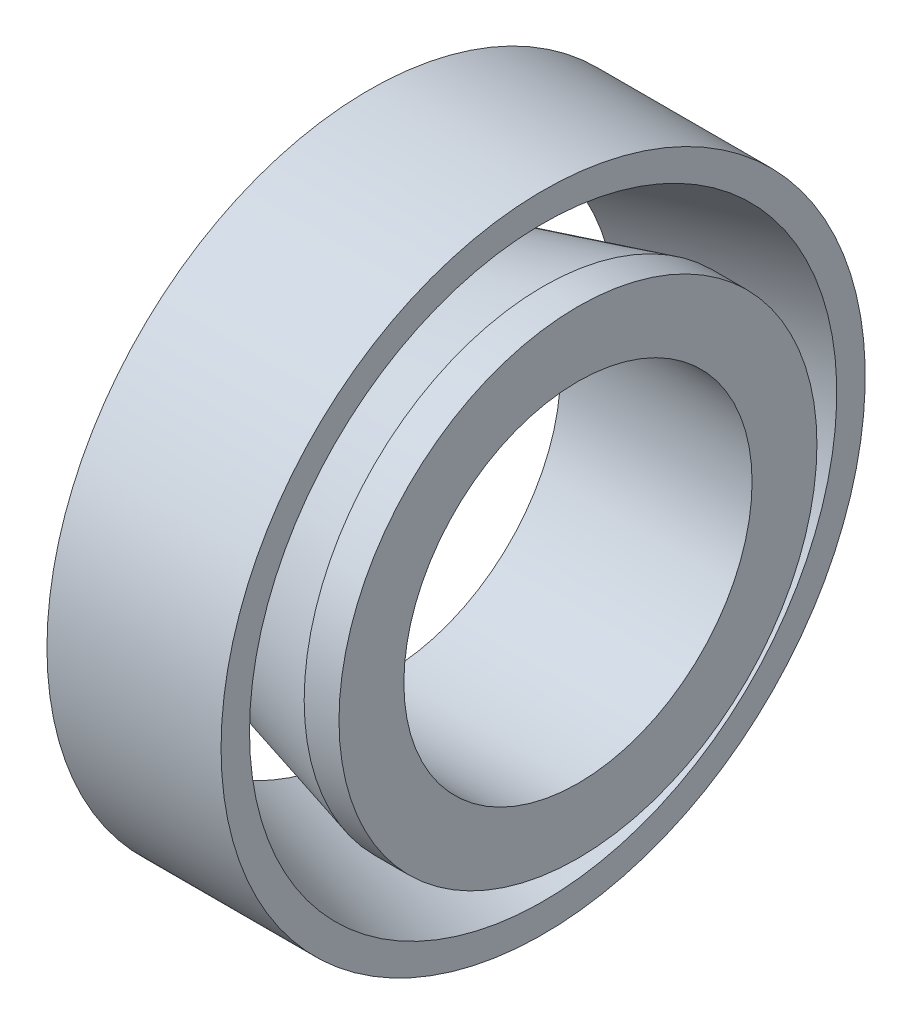
SolidWorks part; units mm, degrees
ref_plane "前视基准面" through (0, 0, 0) normal (0, 0, 1) x (1, 0, 0)
ref_plane "上视基准面" through (0, 0, 0) normal (0, 1, 0) x (1, 0, 0)
ref_plane "右视基准面" through (0, 0, 0) normal (1, 0, 0) x (0, 0, -1)
other "Configuration Table"
sketch "草图3" plane through (0, 0, 0) normal (0, 0, 1) x (1, 0, 0)
  line L0 (0, 0) -> (64.9069, 0) construction
  line L1 (0, 0) -> (0, 18.5) construction
  line L2 (0, 18.5) -> (10, 18.5)
  line L3 (10, 18.5) -> (10, 16.8656)
  line L4 (0, 18.5) -> (0, 14.1862)
  line L5 (0, 14.1862) -> (10, 16.8656)
  line L6 (1, 10) -> (12, 10)
  line L7 (12, 10) -> (12, 13.7257)
  line L8 (12, 13.7257) -> (10, 13.7257)
  line L9 (10, 13.7257) -> (1, 11.3142)
  line L10 (1, 11.3142) -> (1, 10)
  point P9 (0, 0)
  dimension "D1" = 37
  dimension "D2" = 20
  dimension "D3" = 12
  dimension "D4" = 15
  dimension "D5" = 11
  dimension "D6" = 10
  dimension "D7" = 1.6344
revolve "旋转1" add sketch "草图3" angle 360 about L0
